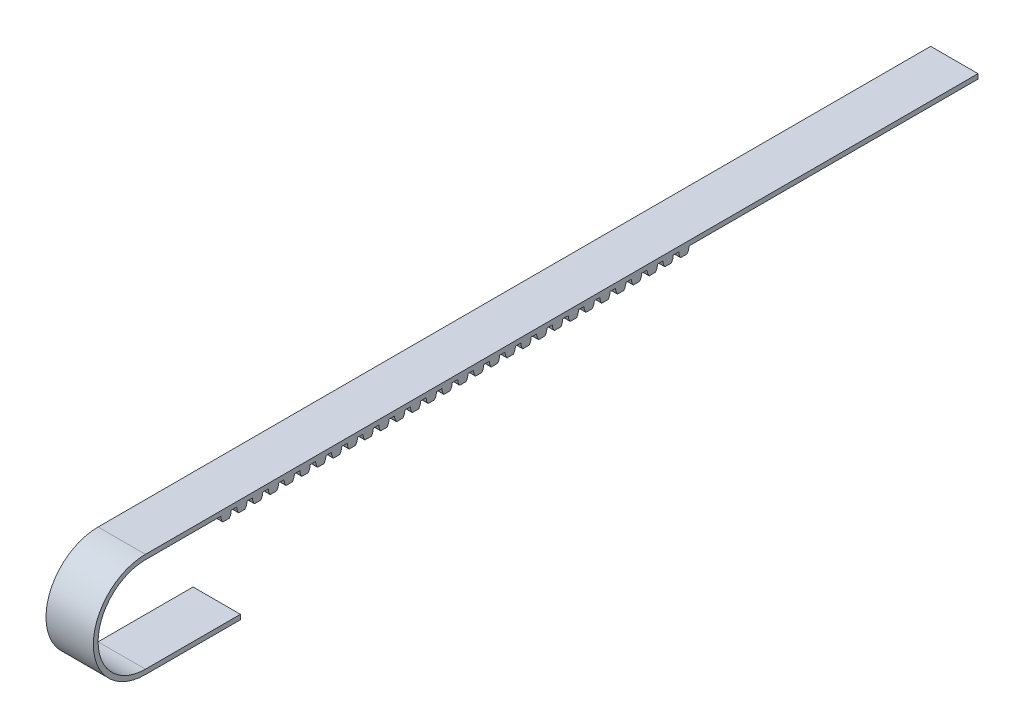
SolidWorks part; units mm, degrees
ref_plane "前视基准面" through (0, 0, 0) normal (0, 0, 1) x (1, 0, 0)
ref_plane "上视基准面" through (0, 0, 0) normal (0, 1, 0) x (1, 0, 0)
ref_plane "右视基准面" through (0, 0, 0) normal (1, 0, 0) x (0, 0, -1)
sketch "草图1" plane through (0, 0, 0) normal (0, 0, 1) x (1, 0, 0)
  line L1 (0, 0) -> (6, 0)
  line L2 (0, 0) -> (0, 0.6)
  line L3 (0, 0.6) -> (6, 0.6)
  line L4 (6, 0) -> (6, 0.6)
  dimension "D1" = 6
  dimension "D2" = 0.6
extrude "凸台-拉伸1" add sketch "草图1" along normal blind 100
sketch "草图2" plane through (6, 0, 0) normal (1, 0, 0) x (0, 0, -1)
  line L0 (-97.2141, -0.76) -> (-93.6093, -0.76) construction
  line L1 (-100, 0) -> (0, 0) construction
  line L2 (-95.9141, -0.76) -> (-95.9141, 1.3855) construction
  line L3 (-95.9141, 0) -> (-94.6141, 0) construction
  line L4 (-95.6688, -0.76) -> (-94.8594, -0.76)
  line L5 (-95.9141, 0) -> (-94.6141, 0)
  arc A0 (-95.2641, 1.1258) -> (-95.9141, 1.3) centre (-95.9141, 0) ccw
  arc A1 (-95.9141, 0) -> (-95.6688, -0.76) centre (-94.6141, 0) ccw
  arc A2 (-94.8594, -0.76) -> (-94.6141, 0) centre (-95.9141, 0) ccw
  line M7 (-100, 0) -> (0, 0)
  dimension "D1" = 0.76
  dimension "D2" = 1.3
extrude "凸台-拉伸2" add sketch "草图2" against normal blind 6 contours L4 A2 A1 M7 region at (6, -0.3534, 95.2641)
pattern_linear "阵列(线性)1" count 30 spacing 2 along (0, 0, -1) of "凸台-拉伸2"
sketch "草图3" plane through (6, 0, 0) normal (1, 0, 0) x (0, 0, -1)
  line L1 (-100, 0) -> (-105.4781, 0)
  line L2 (-100, 0) -> (-100, 0.6)
  line L3 (-100, 0.6) -> (-105.4781, 0.6)
  line L5 (-105.4781, -12) -> (-93.4434, -12)
  line L7 (-105.4781, -12.6) -> (-93.4434, -12.6)
  line L8 (-93.4434, -12) -> (-93.4434, -12.6)
  arc A0 (-105.4781, 0) -> (-105.4781, -12) centre (-105.4781, -6) ccw
  arc A1 (-105.4781, 0.6) -> (-105.4781, -12.6) centre (-105.4781, -6) ccw
  dimension "D1" = 6
extrude "凸台-拉伸3" add sketch "草图3" against normal blind 6
